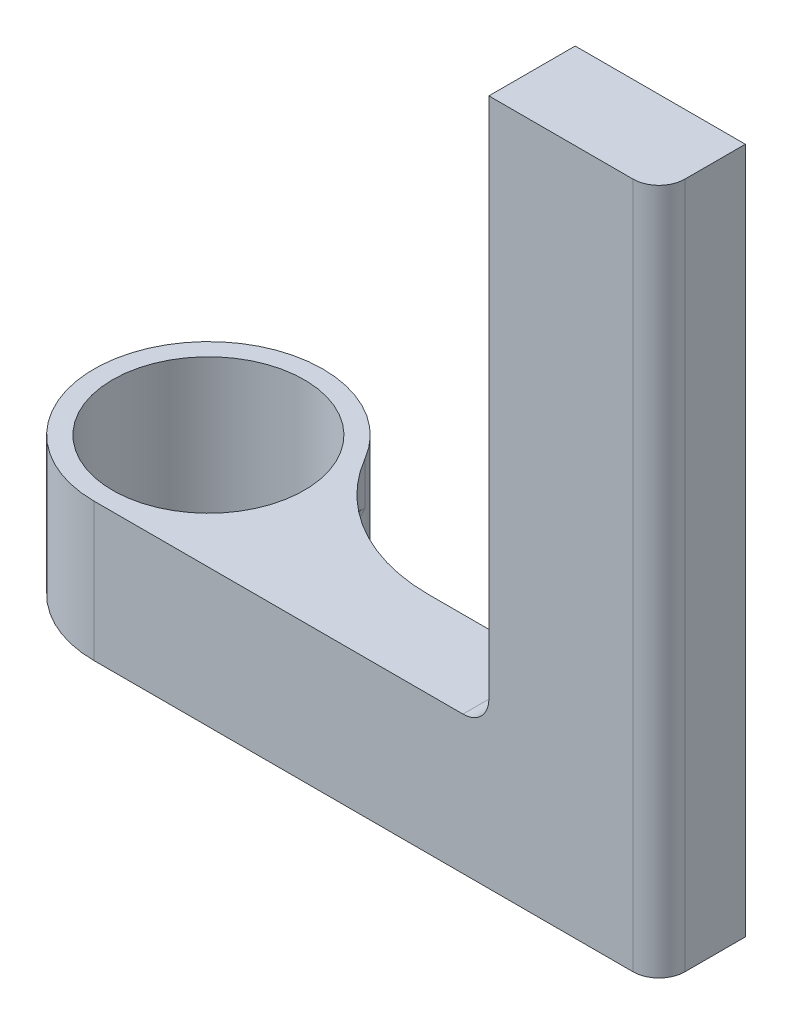
SolidWorks part; units mm, degrees
ref_plane "Front Plane" through (0, 0, 0) normal (0, 0, 1) x (1, 0, 0)
ref_plane "Top Plane" through (0, 0, 0) normal (0, 1, 0) x (1, 0, 0)
ref_plane "Right Plane" through (0, 0, 0) normal (1, 0, 0) x (0, 0, -1)
sketch "Sketch1" plane through (0, 0, 0) normal (0, 0, 1) x (1, 0, 0)
  line L1 (-10.0973, 6.884) -> (6.4027, 6.884)
  line L2 (-10.0973, 6.884) -> (-10.0973, -68.616)
  line L3 (-10.0973, -68.616) -> (6.4027, -68.616)
  line L4 (6.4027, 6.884) -> (6.4027, -68.616)
  line L5 (-11.6973, 8.484) -> (8.0027, 8.484)
  line L6 (-11.6973, 8.484) -> (-11.6973, -70.216)
  line L7 (-11.6973, -70.216) -> (8.0027, -70.216)
  line L8 (8.0027, 8.484) -> (8.0027, -70.216)
  dimension "D1" = 16.5
  dimension "D2" = 75.5
  dimension "D3" = 1.6
  dimension "D4" = 1.6
  dimension "D5" = 1.6
  dimension "D6" = 1.6
extrude "Boss-Extrude1" add sketch "Sketch1" along normal blind 10
sketch "Sketch3" plane through (0, 0, 10) normal (0, 0, 1) x (1, 0, 0)
  line L1 (-11.6973, 8.484) -> (8.0027, 8.484)
  line L2 (-11.6973, 8.484) -> (-11.6973, -70.216)
  line L3 (-11.6973, -70.216) -> (8.0027, -70.216)
  line L4 (8.0027, 8.484) -> (8.0027, -70.216)
extrude "Boss-Extrude2" add sketch "Sketch3" against normal blind 1.5
sketch "Sketch4" plane through (-10.0973, 0, 0) normal (1, 0, 0) x (0, 0, -1)
  line L0 (0, 6.884) -> (0, -68.616) construction
  line L1 (0, -36.866) -> (-8.5, -36.866)
  line L2 (0, -36.866) -> (0, -24.866)
  line L3 (0, -24.866) -> (-8.5, -24.866)
  line L4 (-8.5, -36.866) -> (-8.5, -24.866)
  line L5 (-8.5, 6.884) -> (-8.5, -68.616) construction
  line L6 (0, -24.866) -> (0, 6.884) construction
  line L7 (0, -36.866) -> (0, -68.616) construction
  dimension "D1" = 12
extrude "Cut-Extrude1" cut sketch "Sketch4" against normal blind 10
sketch "Sketch5" plane through (-11.6973, 0, 0) normal (-1, 0, 0) x (0, 0, 1)
  line L0 (0, 8.484) -> (0, -24.866) construction
  line L1 (0, -22.866) -> (10, -22.866)
  line L2 (0, -22.866) -> (0, -24.866)
  line L3 (0, -38.866) -> (10, -38.866)
  line L4 (10, -22.866) -> (10, -38.866)
  line L5 (10, 8.484) -> (10, -70.216) construction
  line L6 (0, -24.866) -> (8.5, -24.866) construction
  line L7 (8.5, -36.866) -> (0, -36.866) construction
  line L8 (0, -36.866) -> (8.5, -36.866)
  line L9 (8.5, -36.866) -> (8.5, -24.866)
  line L10 (8.5, -24.866) -> (0, -24.866)
  line L11 (0, -36.866) -> (0, -38.866)
  dimension "D1" = 2
  dimension "D2" = 2
extrude "Boss-Extrude3" add sketch "Sketch5" along normal blind 27.9
sketch "Sketch6" plane through (0, -22.866, 0) normal (0, 1, 0) x (1, 0, 0)
  line L0 (-39.5973, -10) -> (-11.6973, -10) construction
  line L1 (-11.6973, -10) -> (-11.6973, 0) construction
  circle A0 centre (-57.4214, 3.25) radius 13.25
  point P2 (-79.5214, 1.1548)
  point P5 (0, 0)
  dimension "D1" = 26.5
  dimension "D2" = 45.7242
extrude "Boss-Extrude4" add sketch "Sketch6" against normal up to surface (16 mm away) separate body up to face at (-25.6473, -38.866, 5)
sketch "Sketch7" plane through (-39.5973, 0, 0) normal (-1, 0, 0) x (0, 0, 1)
  line L8 (0, -22.866) -> (0, -24.866)
  line L9 (0, -24.866) -> (8.5, -24.866)
  line L10 (8.5, -24.866) -> (8.5, -36.866)
  line L11 (8.5, -36.866) -> (0, -36.866)
  line L12 (0, -36.866) -> (0, -38.866)
  line L13 (0, -38.866) -> (10, -38.866)
  line L14 (10, -38.866) -> (10, -22.866)
  line L15 (10, -22.866) -> (0, -22.866)
  line L16 (0, -22.866) -> (0, -24.866)
  line L17 (0, -24.866) -> (8.5, -24.866)
  line L18 (8.5, -24.866) -> (8.5, -36.866)
  line L19 (8.5, -36.866) -> (0, -36.866)
  line L20 (0, -36.866) -> (0, -38.866)
  line L21 (0, -38.866) -> (10, -38.866)
  line L22 (10, -38.866) -> (10, -22.866)
  line L23 (10, -22.866) -> (0, -22.866)
  dimension "D1" = 0
extrude "Boss-Extrude5" add sketch "Sketch7" along normal up to next
sketch "Sketch9" plane through (0, -22.866, 0) normal (0, 1, 0) x (1, 0, 0)
  circle A0 centre (-57.4214, 3.25) radius 11.1
  dimension "D1" = 22.2
extrude "Cut-Extrude2" cut sketch "Sketch9" against normal blind 50
fillet "Fillet1" radius 20 2 edges at (-44.5762, -37.866, 0) (-44.5762, -23.866, 0)
fillet "Fillet2" radius 15 1 edges at (-51.2977, -30.866, 8.5)
fillet "Fillet5" radius 3 2 edges at (-11.6973, -38.866, 5) (-11.6973, -22.866, 5)
sketch "Sketch10" plane through (0, 0, 8.5) normal (0, 0, -1) x (-1, 0, 0)
  line L0 (-6.4027, -68.616) -> (-6.4027, 6.884) construction
  line L1 (10.0973, -36.866) -> (-6.4027, -36.866)
  line L2 (10.0973, -36.866) -> (10.0973, -38.866)
  line L3 (10.0973, -38.866) -> (-6.4027, -38.866)
  line L4 (-6.4027, -36.866) -> (-6.4027, -38.866)
  dimension "D1" = 2
extrude "Boss-Extrude6" add sketch "Sketch10" along normal up to surface (8.5 mm away) up to face at (-11.1841, -30.866, 0)
sketch "Sketch11" plane through (0, 0, 8.5) normal (0, 0, -1) x (-1, 0, 0)
  line L0 (10.0973, 6.884) -> (10.0973, -24.866) construction
  line L1 (-6.4027, -36.866) -> (10.0973, -36.866)
  line L2 (-6.4027, -36.866) -> (-6.4027, 38.634)
  line L3 (-6.4027, 38.634) -> (10.0973, 38.634)
  line L4 (10.0973, -36.866) -> (10.0973, 38.634)
  dimension "D1" = 75.5
extrude "Boss-Extrude7" add sketch "Sketch11" against normal up to surface (1.5 mm away) up to face at (-17.3778, -30.866, 10)
sketch "Sketch13" plane through (0, 0, 10) normal (0, 0, 1) x (1, 0, 0)
  line L0 (-11.6973, 8.484) -> (-11.6973, 40.634)
  line L1 (-11.6973, 40.634) -> (8.0027, 40.634)
  line L2 (8.0027, 40.634) -> (8.0027, 8.484)
  line L3 (8.0027, 8.484) -> (6.4027, 8.484)
  line L4 (6.4027, 8.484) -> (6.4027, 38.634)
  line L5 (6.4027, 38.634) -> (-10.0973, 38.634)
  line L6 (-10.0973, 38.634) -> (-10.0973, 8.484)
  line L7 (-10.0973, 8.484) -> (-11.6973, 8.484)
  dimension "D1" = 2
extrude "Boss-Extrude8" add sketch "Sketch13" against normal up to surface (10 mm away) up to face at (-11.3199, -26.1472, 0)
sketch "Sketch14" plane through (0, -38.866, 0) normal (0, -1, 0) x (-1, 0, 0)
  circle A0 centre (2.3259, -5.062) radius 41.2181
extrude "Cut-Extrude3" cut sketch "Sketch14" along normal blind 83
sketch "Sketch15" plane through (0, 0, 8.5) normal (0, 0, -1) x (-1, 0, 0)
  line L1 (10.0973, 6.884) -> (-6.4027, 6.884)
  line L2 (10.0973, 6.884) -> (10.0973, 8.484)
  line L3 (10.0973, 8.484) -> (-6.4027, 8.484)
  line L4 (-6.4027, 6.884) -> (-6.4027, 8.484)
extrude "Cut-Extrude4" cut sketch "Sketch15" along normal blind 122
fillet "Fillet7" radius 3 10 edges at (-44.8508, -24.866, -7.4384) (-39.3369, -24.866, 4.7001) (-44.8508, -36.866, -7.4384) (-39.3369, -36.866, 4.7001) (8.0027, 0.884, 10) (-19.7281, -24.866, 8.5) (-11.4781, -36.866, 8.5) (6.4027, 0.884, 8.5) (-1.8473, 38.634, 8.5) (-10.0973, 6.884, 8.5)
